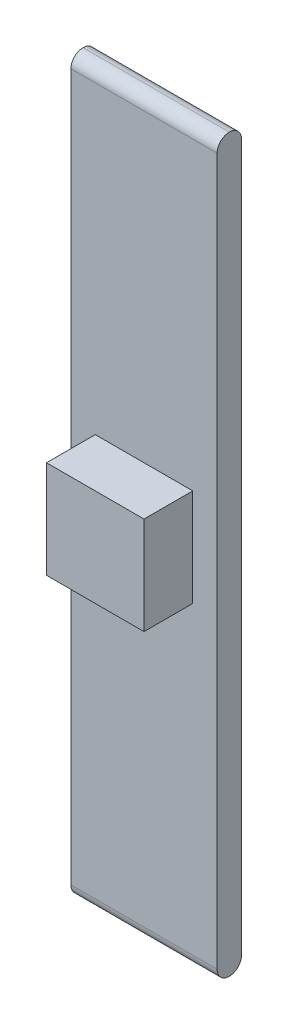
SolidWorks part; units mm, degrees
ref_plane "Front Plane" through (0, 0, 0) normal (0, 0, 1) x (1, 0, 0)
ref_plane "Top Plane" through (0, 0, 0) normal (0, 1, 0) x (1, 0, 0)
ref_plane "Right Plane" through (0, 0, 0) normal (1, 0, 0) x (0, 0, -1)
sketch "Sketch1" plane through (0, 0, 0) normal (0, 0, 1) x (1, 0, 0)
  line L1 (300, 1500) -> (-300, 1500)
  line L2 (300, 1500) -> (300, -1500)
  line L3 (300, -1500) -> (-300, -1500)
  line L4 (-300, 1500) -> (-300, -1500)
  line L5 (300, 1500) -> (-300, -1500) construction
  line L6 (300, -1500) -> (-300, 1500) construction
  point P0 (0, 0)
  point P6 (0, 0)
  dimension "D1" = 3000
  dimension "D2" = 600
extrude "Boss-Extrude2" add sketch "Sketch1" against normal blind 100 contours L2 L3 L4 L1
fillet "Fillet2" radius 50 4 edges at (0, 1500, -100) (0, 1500, 0) (0, -1500, -100) (0, -1500, 0)
sketch "Sketch2" plane through (0, 0, 0) normal (0, 0, 1) x (1, 0, 0)
  line L1 (-200, -200) -> (200, -200)
  line L2 (-200, -200) -> (-200, 200)
  line L3 (-200, 200) -> (200, 200)
  line L4 (200, -200) -> (200, 200)
  line L5 (-200, -200) -> (200, 200) construction
  line L6 (-200, 200) -> (200, -200) construction
  point P0 (0, 0)
  dimension "D1" = 400
  dimension "D2" = 400
extrude "Boss-Extrude3" add sketch "Sketch2" along normal blind 200
sketch "Sketch4" plane through (0, 0, 0) normal (0, 1, 0) x (1, 0, 0)
  line L0 (0, 0) -> (0, 200)
